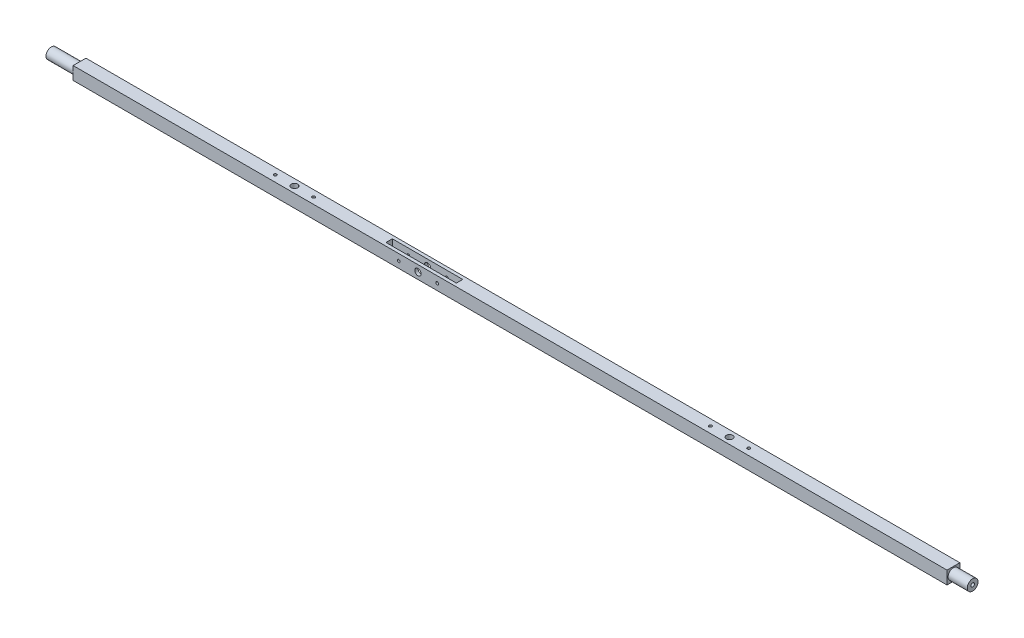
SolidWorks part; units mm, degrees
material "6061-T6 (SS)"
ref_plane "Front Plane" through (0, 0, 0) normal (0, 0, 1) x (1, 0, 0)
ref_plane "Top Plane" through (0, 0, 0) normal (0, 1, 0) x (1, 0, 0)
ref_plane "Right Plane" through (0, 0, 0) normal (1, 0, 0) x (0, 0, -1)
sketch "Sketch1" plane through (0, 0, 0) normal (1, 0, 0) x (0, 0, -1)
  line L1 (-6.35, -6.4107) -> (6.35, -6.4107)
  line L2 (-6.35, -6.4107) -> (-6.35, 6.4107)
  line L3 (-6.35, 6.4107) -> (6.35, 6.4107)
  line L4 (6.35, -6.4107) -> (6.35, 6.4107)
  line L5 (-6.35, -6.4107) -> (6.35, 6.4107) construction
  line L6 (-6.35, 6.4107) -> (6.35, -6.4107) construction
  point P0 (0, 0)
  dimension "D1" = 12.7
  dimension "D2" = 12.8213
extrude "Length" add sketch "Sketch1" along normal mid plane 914.4
ref_plane "Top" through (457.2, 0, 0) normal (1, 0, 0) x (0, 0, -1)
sketch "Sketch2" plane through (457.2, 0, 0) normal (1, 0, 0) x (0, 0, -1)
  line L5 (-3.7537, -3.7896) -> (2.2344, 2.2557) construction
  line L6 (-3.7537, 3.7896) -> (3.7537, -3.7896) construction
  line L7 (-6.35, -6.4107) -> (6.35, -6.4107)
  line L8 (-6.35, -6.4107) -> (-6.35, 6.4107)
  line L9 (-6.35, 6.4107) -> (6.35, 6.4107)
  line L10 (6.35, -6.4107) -> (6.35, 6.4107)
  line L11 (-6.35, -6.4107) -> (6.35, 6.4107) construction
  line L12 (-6.35, 6.4107) -> (6.35, -6.4107) construction
  circle A0 centre (0, 0) radius 5.334
  point P0 (0, 0)
  dimension "D1" = 10.668
extrude "Round Cut 1" cut sketch "Sketch2" against normal blind 19.05 contours L7 L10 L9 L8 A0 region at (457.2, 0, 6.1695)
ref_plane "Bottom Plane" through (-457.2, 0, 0) normal (-1, 0, 0) x (0, 0, 1)
sketch "Sketch3" plane through (-457.2, 0, 0) normal (-1, 0, 0) x (0, 0, 1)
  line L1 (-6.35, -6.4107) -> (6.35, -6.4107)
  line L2 (-6.35, -6.4107) -> (-6.35, 6.4107)
  line L3 (-6.35, 6.4107) -> (6.35, 6.4107)
  line L4 (6.35, -6.4107) -> (6.35, 6.4107)
  line L5 (-6.35, -6.4107) -> (6.35, 6.4107) construction
  line L6 (-6.35, 6.4107) -> (6.35, -6.4107) construction
  circle A0 centre (0, 0) radius 5.334
  point P0 (0, 0)
  dimension "D1" = 10.668
extrude "Round Cut 2" cut sketch "Sketch3" against normal blind 27.94 contours L1 L4 L3 L2 A0 | L2 L1 L4 L3 | A0 region at (-457.2, 0, -6.1695)
ref_plane "Plane13" through (0, -6.4107, 0) normal (0, -1, 0) x (-1, 0, 0)
sketch "Sketch9" plane through (0, -6.4107, 0) normal (0, -1, 0) x (-1, 0, 0)
  line L0 (-438.15, 6.35) -> (429.26, 6.35) construction
  line L1 (-330.2, 6.35) -> (-279.4, 6.35)
  line L2 (-330.2, 6.35) -> (-330.2, -6.35)
  line L3 (-330.2, -6.35) -> (-279.4, -6.35)
  line L4 (-279.4, 6.35) -> (-279.4, -6.35)
  line L5 (-438.15, -6.35) -> (429.26, -6.35) construction
  line L6 (-457.2, 6.985) -> (-457.2, -6.985) construction
  dimension "D1" = 50.8
  dimension "D2" = 127
sketch "Sketch10" plane through (0, -6.4107, 0) normal (0, -1, 0) x (-1, 0, 0)
  line L0 (457.2, -5.334) -> (457.2, 5.334) construction
  line L1 (101.6, -4.7642) -> (406.4, -4.7642)
  line L2 (101.6, -4.7642) -> (101.6, 4.6338)
  line L3 (101.6, 4.6338) -> (406.4, 4.6338)
  line L4 (406.4, -4.7642) -> (406.4, 4.6338)
  line L5 (101.6, -4.7642) -> (406.4, 4.6338) construction
  line L6 (101.6, 4.6338) -> (406.4, -4.7642) construction
  point P0 (254, -0.0652)
  dimension "D1" = 9.398
  dimension "D2" = 304.8
  dimension "D3" = 203.2
extrude "Cut-Extrude2" [suppressed] cut sketch "Sketch10" against normal blind 7.5438
ref_plane "Plane14" through (0, 0, 6.35) normal (0, 0, 1) x (1, 0, 0)
sketch "Sketch11" [suppressed] plane through (0, 0, 6.35) normal (0, 0, 1) x (1, 0, 0)
  line L0 (-50.8, 1.1331) -> (-355.6, 1.1331) construction
  line L1 (-355.6, 1.1331) -> (-355.6, -6.4107) construction
  line L2 (-349.25, -2.6769) -> (-63.4679, -2.6769) construction
  circle A0 centre (-349.25, -2.6769) radius 1.2573
  circle A1 centre (-336.55, -2.6769) radius 1.2573
  circle A2 centre (-323.85, -2.6769) radius 1.2573
  circle A3 centre (-311.15, -2.6769) radius 1.2573
  circle A4 centre (-298.45, -2.6769) radius 1.2573
  circle A5 centre (-285.75, -2.6769) radius 1.2573
  circle A6 centre (-273.05, -2.6769) radius 1.2573
  circle A7 centre (-260.35, -2.6769) radius 1.2573
  circle A8 centre (-247.65, -2.6769) radius 1.2573
  circle A9 centre (-234.95, -2.6769) radius 1.2573
  circle A10 centre (-222.25, -2.6769) radius 1.2573
  circle A11 centre (-209.55, -2.6769) radius 1.2573
  circle A12 centre (-196.85, -2.6769) radius 1.2573
  circle A13 centre (-184.15, -2.6769) radius 1.2573
  circle A14 centre (-171.45, -2.6769) radius 1.2573
  circle A15 centre (-158.75, -2.6769) radius 1.2573
  circle A16 centre (-146.05, -2.6769) radius 1.2573
  circle A17 centre (-133.35, -2.6769) radius 1.2573
  circle A18 centre (-120.65, -2.6769) radius 1.2573
  circle A19 centre (-107.95, -2.6769) radius 1.2573
  circle A20 centre (-95.25, -2.6769) radius 1.2573
  circle A21 centre (-82.55, -2.6769) radius 1.2573
  circle A22 centre (-69.85, -2.6769) radius 1.2573
  circle A23 centre (-57.15, -2.6769) radius 1.2573
  dimension "D1" = 2.5146
  dimension "D2" = 3.81
  dimension "D3" = 24
  dimension "25" = 6.35
extrude "Cut-Extrude3" [suppressed] cut sketch "Sketch11" against normal through all
sketch "Sketch12" plane through (0, -6.4107, 0) normal (0, -1, 0) x (-1, 0, 0)
  line L1 (0, 3.175) -> (-38.1, 3.175)
  line L2 (0, 3.175) -> (0, -3.175)
  line L3 (0, -3.175) -> (-38.1, -3.175)
  line L4 (-38.1, 3.175) -> (-38.1, -3.175)
  dimension "D1" = 38.1
  dimension "D2" = 6.35
  dimension "D3" = 3.175
  dimension "D4" = 0
extrude "Cut-Extrude4" [suppressed] cut sketch "Sketch12" against normal blind 6.35
sketch "Sketch13" [suppressed] plane through (0, 0, 6.35) normal (0, 0, 1) x (1, 0, 0)
  line L0 (0, -0.0607) -> (0, -6.4107) construction
  line L1 (378.46, -6.4107) -> (-378.46, -6.4107) construction
  circle A0 centre (5.08, -3.2357) radius 1.2573
  circle A1 centre (13.97, -3.2357) radius 1.2573
  circle A2 centre (22.86, -3.2357) radius 1.2573
  circle A3 centre (31.75, -3.2357) radius 1.2573
  dimension "D1" = 2.5146
  dimension "D3" = 5.08
  dimension "D4" = 3.175
  dimension "D2" = 4
extrude "Cut-Extrude5" [suppressed] cut sketch "Sketch13" against normal through all
sketch "Sketch14" plane through (457.2, 0, 0) normal (1, 0, 0) x (0, 0, -1)
  circle A0 centre (0, 0) radius 1.7526
  dimension "D1" = 3.5052
extrude "Cut-Extrude6" cut sketch "Sketch14" against normal blind 12.7
sketch "Sketch15" plane through (-457.2, 0, 0) normal (-1, 0, 0) x (0, 0, 1)
  circle A0 centre (0, 0) radius 1.7526
  dimension "D1" = 3.5052
extrude "Cut-Extrude7" cut sketch "Sketch15" against normal blind 19.05
ref_plane "Plane15" through (0, 6.4107, 0) normal (0, 1, 0) x (1, 0, 0)
sketch "Bottom Washer" plane through (0, 6.4107, 0) normal (0, 1, 0) x (1, 0, 0)
  line L1 (-457.2, 5.334) -> (-457.2, -5.334) construction
  circle A1 centre (-196.85, 0) radius 1.4224
  circle A2 centre (-234.95, 0) radius 1.4224
  dimension "D4" = 2.8448
  dimension "D5" = 2.8448
  dimension "D1" = 222.25
  dimension "D2" = 38.1
extrude "Bottom washer bolts" cut sketch "Bottom Washer" against normal blind 10.922 contours A1 | A2 region at (-196.85, 6.4107, 0) region at (-234.95, 6.4107, 0)
sketch "Sketch18" plane through (0, 6.4107, 0) normal (0, 1, 0) x (1, 0, 0)
  line L0 (-457.2, 5.334) -> (-457.2, -5.334) construction
  circle A0 centre (-215.9, 0) radius 3.175
  dimension "D1" = 6.35
  dimension "D2" = 241.3
extrude "Bottom Washer Center Bolt" cut sketch "Sketch18" against normal up to next
sketch "Sketch17" plane through (0, 6.4107, 0) normal (0, 1, 0) x (1, 0, 0)
  line L0 (457.2, -5.334) -> (457.2, 5.334) construction
  circle A0 centre (215.9, 0) radius 3.175
  dimension "D1" = 6.35
  dimension "D2" = 241.3
extrude "Top Washer Center Bolt" cut sketch "Sketch17" against normal up to next
sketch "Sketch16" plane through (0, 6.4107, 0) normal (0, 1, 0) x (1, 0, 0)
  line L0 (457.2, -5.334) -> (457.2, 5.334) construction
  circle A1 centre (234.95, 0) radius 1.4224
  circle A2 centre (196.85, 0) radius 1.4224
  dimension "D1" = 38.1
  dimension "D3" = 2.8448
  dimension "D4" = 2.8448
  dimension "D2" = 222.25
extrude "Top Washer" cut sketch "Sketch16" against normal blind 10.922
ref_plane "Plane16" through (0, -6.4107, 0) normal (0, -1, 0) x (-1, 0, 0)
sketch "Sketch19" plane through (0, -6.4107, 0) normal (0, -1, 0) x (-1, 0, 0)
  line L0 (-438.15, 6.35) -> (429.26, 6.35) construction
  line L1 (52.0606, 3.175) -> (121.9106, 3.175)
  line L2 (52.0606, 3.175) -> (52.0606, -3.175)
  line L3 (52.0606, -3.175) -> (121.9106, -3.175)
  line L4 (121.9106, 3.175) -> (121.9106, -3.175)
  line L5 (429.26, 6.35) -> (429.26, -6.35) construction
  dimension "D1" = 6.35
  dimension "D2" = 3.175
  dimension "D3" = 69.85
  dimension "D4" = 307.3494
extrude "Cut-Extrude8" cut sketch "Sketch19" against normal through all
ref_plane "Plane17" through (0, 0, 6.35) normal (0, 0, 1) x (1, 0, 0)
sketch "Sketch20" plane through (0, 0, 6.35) normal (0, 0, 1) x (1, 0, 0)
  line L0 (-86.9856, 6.4107) -> (-86.9856, -6.4107) construction
  line L1 (-52.0606, 6.4107) -> (-52.0606, -6.4107) construction
  line L3 (-121.9106, 0) -> (-52.0606, 0) construction
  line L6 (-121.9106, -6.4107) -> (-52.0606, -6.4107)
  line L7 (-121.9106, 6.4107) -> (-121.9106, -6.4107)
  line L8 (-52.0606, 6.4107) -> (-121.9106, 6.4107)
  line L9 (-52.0606, -6.4107) -> (-52.0606, 6.4107)
  line L10 (-121.9106, -6.4107) -> (-52.0606, -6.4107) construction
  line L11 (-121.9106, 6.4107) -> (-121.9106, -6.4107) construction
  line L12 (-52.0606, 6.4107) -> (-121.9106, 6.4107) construction
  line L13 (-52.0606, -6.4107) -> (-52.0606, 6.4107) construction
  circle A0 centre (-106.0356, 0) radius 1.397
  circle A1 centre (-86.9856, 0) radius 3.175
  circle A2 centre (-67.9356, 0) radius 1.397
  dimension "D1" = 2.794
  dimension "D2" = 6.35
  dimension "D3" = 2.794
  dimension "D4" = 15.875
  dimension "D5" = 19.05
  dimension "D6" = 19.05
  dimension "D7" = 0
extrude "Cut-Extrude9" cut sketch "Sketch20" against normal through all
equation "\"Diameter\"= .420"
equation "\"Round Cut Depth Top\"= .75"
equation "\"Stringer Length\"=36"
equation "\"D1@Sketch3\"= \"Diameter\""
equation "\"D1@Sketch2\"= \"Diameter\""
equation "\"D1@Round Cut 1\"= \"Round Cut Depth Top\""
equation "\"D1@Round Cut 2\" = \"Round Cut Depth Bottom\""
equation "\"D1@Length\"= \"Stringer Length\""
equation "\"Round Cut Depth Bottom\"= 1.1"
